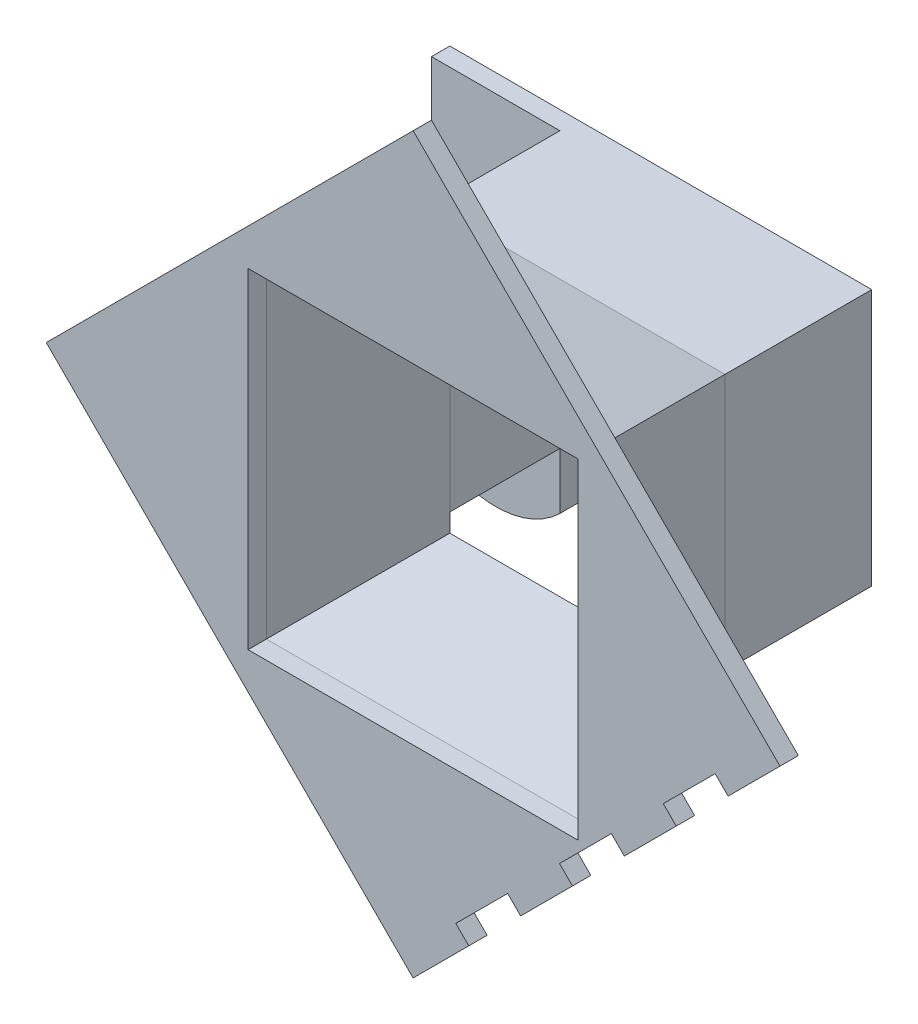
SolidWorks part; units mm, degrees
material "ABS"
ref_plane "Front Plane" through (0, 0, 0) normal (0, 0, 1) x (1, 0, 0)
ref_plane "Top Plane" through (0, 0, 0) normal (0, 1, 0) x (1, 0, 0)
ref_plane "Right Plane" through (0, 0, 0) normal (1, 0, 0) x (0, 0, -1)
sketch "Sketch2" plane through (0, 0, 0) normal (0, 0, 1) x (1, 0, 0)
  line L0 (0, 0) -> (69.8407, 0) construction
  line L1 (-50.8, 50.8) -> (50.8, 50.8)
  line L2 (-50.8, 50.8) -> (-50.8, -50.8)
  line L3 (-50.8, -50.8) -> (50.8, -50.8)
  line L4 (50.8, 50.8) -> (50.8, -50.8)
  line L5 (0, 0) -> (0, -80.5593) construction
  dimension "D1" = 101.6
ref_plane "Plane1" through (0, 0, 50.8) normal (0, 0, 1) x (1, 0, 0)
sketch "Sketch3" plane through (0, 0, 50.8) normal (0, 0, 1) x (1, 0, 0)
  line L0 (0, 0) -> (0, 42.9934) construction
  line L1 (-63.5, 63.5) -> (63.5, 63.5)
  line L2 (-63.5, 63.5) -> (-63.5, -63.5)
  line L3 (-63.5, -63.5) -> (63.5, -63.5)
  line L4 (63.5, 63.5) -> (63.5, -63.5)
  line L7 (0, 0) -> (38.1349, 0) construction
  dimension "D1" = 127
loft "Loft1" add profiles "Sketch2", "Sketch3" connector at (50.8, 50.8, 0) connector at (63.5, 63.5, 50.8)
sketch "Sketch4" plane through (0, 0, 50.8) normal (0, 0, 1) x (1, 0, 0)
  line L14 (-57.15, -57.15) -> (57.15, -57.15)
  line L15 (57.15, -57.15) -> (57.15, 57.15)
  line L16 (57.15, 57.15) -> (-57.15, 57.15)
  line L17 (-57.15, 57.15) -> (-57.15, -57.15)
  line L18 (-57.15, -57.15) -> (57.15, -57.15)
  line L19 (57.15, -57.15) -> (57.15, 57.15)
  line L20 (57.15, 57.15) -> (-57.15, 57.15)
  line L21 (-57.15, 57.15) -> (-57.15, -57.15)
  dimension "D1" = 6.35
sketch "Sketch5" plane through (0, 0, 0) normal (0, 0, -1) x (-1, 0, 0)
  line L14 (-44.45, -44.45) -> (44.45, -44.45)
  line L15 (44.45, -44.45) -> (44.45, 44.45)
  line L16 (44.45, 44.45) -> (-44.45, 44.45)
  line L17 (-44.45, 44.45) -> (-44.45, -44.45)
  line L18 (-44.45, -44.45) -> (44.45, -44.45)
  line L19 (44.45, -44.45) -> (44.45, 44.45)
  line L20 (44.45, 44.45) -> (-44.45, 44.45)
  line L21 (-44.45, 44.45) -> (-44.45, -44.45)
  dimension "D1" = 6.35
loft "Cut-Loft1" cut profiles "Sketch5", "Sketch4" connector at (-44.45, 44.45, 0) connector at (-57.15, 57.15, 50.8)
sketch "Sketch6" plane through (0, 0, 0) normal (0, 0, -1) x (-1, 0, 0)
  line L0 (44.45, -38.1) -> (50.8, -38.1)
  line L1 (44.45, -44.45) -> (44.45, 44.45) construction
  line L2 (50.8, 50.8) -> (50.8, -50.8) construction
  line L3 (50.8, -38.1) -> (50.8, 50.8)
  line L4 (50.8, 50.8) -> (-50.8, 50.8)
  line L5 (-50.8, 50.8) -> (-50.8, -38.1)
  line L6 (-50.8, -50.8) -> (-50.8, 50.8) construction
  line L7 (-50.8, -38.1) -> (-44.45, -38.1)
  line L8 (-44.45, 44.45) -> (-44.45, -44.45) construction
  line L9 (-44.45, -38.1) -> (-44.45, 44.45)
  line L10 (-44.45, 44.45) -> (44.45, 44.45)
  line L11 (44.45, 44.45) -> (44.45, -38.1)
  line L13 (-44.45, -38.1) -> (-38.1, -38.1) construction
extrude "Boss-Extrude1" add sketch "Sketch6" along normal blind 50.8
sketch "Sketch7" plane through (0, 0, -50.8) normal (0, 0, -1) x (-1, 0, 0)
  line L0 (50.8, 50.8) -> (-50.8, 50.8) construction
  line L1 (44.45, -38.1) -> (95.25, -38.1)
  line L2 (44.45, -38.1) -> (44.45, 50.8)
  line L3 (44.45, 50.8) -> (95.25, 50.8)
  line L4 (95.25, -38.1) -> (95.25, 50.8)
  dimension "D1" = 50.8
extrude "Boss-Extrude2" add sketch "Sketch7" against normal blind 6.35
sketch "Sketch8" plane through (0, 0, -44.45) normal (0, 0, 1) x (1, 0, 0)
  line L0 (-50.8, 50.8) -> (-50.8, -38.1) construction
  line L1 (-95.25, -38.1) -> (-50.8, -38.1)
  line L2 (-95.25, -38.1) -> (-95.25, -76.2)
  line L3 (-95.25, -76.2) -> (-50.8, -76.2)
  line L4 (-50.8, -38.1) -> (-50.8, -76.2)
  dimension "D1" = 38.1
extrude "Boss-Extrude3" add sketch "Sketch8" against normal up to surface (6.35 mm away) up to face at (-11.1125, 4.7625, -50.8)
fillet "Fillet1" [suppressed] radius 35.56
sketch "Sketch9" plane through (0, 0, -44.45) normal (0, 0, 1) x (1, 0, 0)
  line L0 (-73.025, 27.6092) -> (-73.025, -57.5144) construction
  line L3 (-62.992, -50.3) -> (-62.992, -11.041) construction
  line L4 (-83.185, -10.3505) -> (-62.865, -10.3505)
  line L5 (-83.185, -10.3505) -> (-83.185, -50.9905)
  line L6 (-83.185, -50.9905) -> (-62.865, -50.9905)
  line L7 (-62.865, -10.3505) -> (-62.865, -50.9905)
  line L8 (-83.058, -11.041) -> (-83.058, -50.3) construction
  line L9 (-89.9768, -30.6705) -> (-55.7405, -30.6705) construction
  line L10 (-82.558, -50.8) -> (-63.492, -50.8) construction
  line L11 (-63.492, -10.541) -> (-82.558, -10.541) construction
  dimension "D1" = 20.32
  dimension "D2" = 40.64
fillet "Fillet2" [suppressed] radius 2.54
extrude "Cut-Extrude1" cut sketch "Sketch9" against normal through all
sketch "Sketch10" plane through (0, 0, -44.45) normal (0, 0, 1) x (1, 0, 0)
  circle A0 centre (-68.025, -6.1705) radius 1.778
  circle A1 centre (-78.025, -6.1705) radius 1.778
  circle A2 centre (-78.025, -55.1705) radius 1.778
  circle A3 centre (-68.025, -55.1705) radius 1.778
  arc A4 (-76.755, -56.4148) -> (-79.295, -56.4148) centre (-78.025, -55.1705) ccw construction
  arc A5 (-66.755, -56.4148) -> (-69.295, -56.4148) centre (-68.025, -55.1705) ccw construction
  arc A6 (-79.295, -4.9262) -> (-76.755, -4.9262) centre (-78.025, -6.1705) ccw construction
  arc A7 (-69.295, -4.9262) -> (-66.755, -4.9262) centre (-68.025, -6.1705) ccw construction
extrude "Cut-Extrude2" cut sketch "Sketch10" against normal through all
sketch "Sketch11" plane through (0, 0, -44.45) normal (0, 0, 1) x (1, 0, 0)
  line L0 (-50.8, -76.2) -> (-95.25, -76.2)
  line L1 (-95.25, -76.2) -> (-50.8, -76.2) construction
  line L2 (-95.25, -76.2) -> (-95.25, -63.949)
  line L3 (-95.25, -76.2) -> (-95.25, 50.8) construction
  line L4 (-50.8, -76.2) -> (-50.8, -63.949)
  line L5 (-50.8, -76.2) -> (-50.8, -38.1) construction
  circle A0 centre (-73.025, -41.275) radius 31.75
  circle A1 centre (-73.025, -41.275) radius 6.25 construction
  line M11 (-95.25, 50.8) -> (-95.25, -76.2)
  line M12 (-95.25, -76.2) -> (-50.8, -76.2)
  line M13 (-50.8, -76.2) -> (-50.8, -38.1)
  dimension "D1" = 63.5
extrude "Cut-Extrude3" cut sketch "Sketch11" against normal blind 6.35 contours A0 M11 M12 M13 region at (-73.025, -75.7389, -44.45)
sketch "Sketch12" plane through (0, 0, 50.8) normal (0, 0, 1) x (1, 0, 0)
  line L0 (127, 0) -> (0, -127)
  line L1 (127, 0) -> (0, 127)
  line L2 (0, -127) -> (-127, 0)
  line L3 (0, 127) -> (-127, 0)
  line L4 (-63.5, -63.5) -> (63.5, -63.5) construction
  line L5 (0, 0) -> (-106.6892, -106.6892) construction
  line L6 (0, 0) -> (125.9109, -125.9109) construction
  line L7 (63.5, -63.5) -> (63.5, 63.5) construction
  line L8 (-63.5, 63.5) -> (-63.5, -63.5) construction
  line L9 (63.5, 63.5) -> (-63.5, 63.5) construction
  line L10 (63.5, -63.5) -> (63.5, 63.5)
  line L11 (-63.5, -63.5) -> (63.5, -63.5)
  line L12 (-63.5, 63.5) -> (-63.5, -63.5)
  line L13 (63.5, 63.5) -> (-63.5, 63.5)
  line L14 (57.15, -57.15) -> (57.15, 57.15) construction
  line L15 (-57.15, -57.15) -> (57.15, -57.15) construction
  line L16 (-57.15, 57.15) -> (-57.15, -57.15) construction
  line L17 (57.15, 57.15) -> (-57.15, 57.15) construction
  line L18 (57.15, -57.15) -> (57.15, 57.15)
  line L19 (-57.15, -57.15) -> (57.15, -57.15)
  line L20 (-57.15, 57.15) -> (-57.15, -57.15)
  line L21 (57.15, 57.15) -> (-57.15, 57.15)
  line M11 (57.15, -57.15) -> (-57.15, -57.15)
  line M12 (-57.15, -57.15) -> (-57.15, 57.15)
  line M13 (-57.15, 57.15) -> (57.15, 57.15)
  line M14 (57.15, 57.15) -> (57.15, -57.15)
  dimension "D1" = 45
extrude "Boss-Extrude5" add sketch "Sketch12" along normal blind 6.35 contours L0 L1 | M14 M11 M12 M13 | L2 L0 | L3 L2 | L1 L3 region at (84.6667, 0, 50.8) region at (0, -61.7039, 50.8) region at (0, -84.6667, 50.8) region at (0, 84.6667, 50.8) region at (-84.6667, 0, 50.8)
sketch "Sketch13" plane through (0, 0, 50.8) normal (0, 0, -1) x (-1, 0, 0)
  line L0 (-19.2651, -107.7349) -> (-14.775, -103.2448)
  line L1 (-19.2651, -107.7349) -> (-37.2071, -89.7929)
  line L2 (-14.775, -103.2448) -> (-32.7169, -85.3028)
  line L3 (-37.2071, -89.7929) -> (-32.7169, -85.3028)
  line L4 (-63.5, -63.5) -> (0, -127) construction
  line L5 (-55.158, -71.842) -> (-50.6678, -67.3519)
  line L6 (-55.158, -71.842) -> (-73.105, -53.895)
  line L7 (-50.6678, -67.3519) -> (-68.6149, -49.4049)
  line L8 (-73.105, -53.895) -> (-68.6149, -49.4049)
  line L9 (-91.079, -35.921) -> (-86.5888, -31.4309)
  line L10 (-91.079, -35.921) -> (-109.0262, -17.9738)
  line L11 (-86.5888, -31.4309) -> (-104.5361, -13.4836)
  line L12 (-109.0262, -17.9738) -> (-104.5361, -13.4836)
  line L13 (-127, 0) -> (-63.5, -63.5) construction
extrude "Cut-Extrude4" cut sketch "Sketch13" against normal through all both and the other way through all
